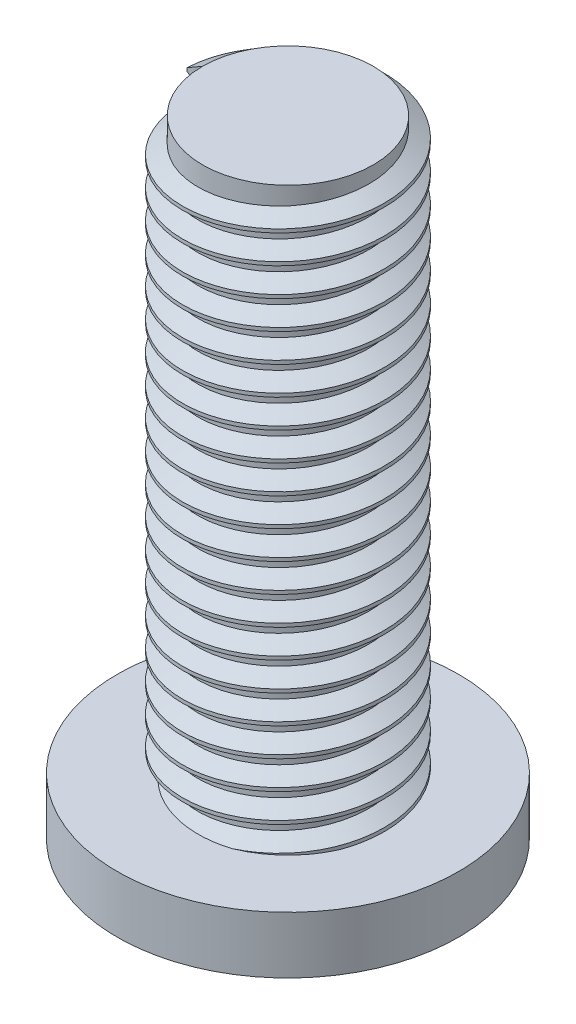
SolidWorks part; units mm, degrees
material "AISI Type A2 Tool Steel"
ref_plane "Front Plane" through (0, 0, 0) normal (0, 0, 1) x (1, 0, 0)
ref_plane "Top Plane" through (0, 0, 0) normal (0, 1, 0) x (1, 0, 0)
ref_plane "Right Plane" through (0, 0, 0) normal (1, 0, 0) x (0, 0, -1)
sketch "Sketch1" plane through (0, 0, 0) normal (0, 1, 0) x (1, 0, 0)
  circle A0 centre (0, 0) radius 1.5
  dimension "D1" = 3
extrude "Boss-Extrude1" add sketch "Sketch1" along normal blind 10
sketch "Sketch2" plane through (0, 0, 0) normal (0, -1, 0) x (1, 0, 0)
  circle A0 centre (0, 0) radius 3
  dimension "D1" = 6
extrude "Boss-Extrude2" add sketch "Sketch2" along normal blind 1
thread "Thread1" pitch 0.5 method extrude profile "Thread Profile1" start angle 0, offset 0, length 0, pitch 0.5, diameter 3
ref_plane "Plane1" through (-1.5, 10, 0) normal (0, 0, 1) x (-1, 0, 0)
sketch "Thread Profile1" plane through (-1.5, 10, 0) normal (0, 0, 1) x (-1, 0, 0)
  line L0 (0, 0) -> (0, 0.5) construction
  line L1 (0, 0) -> (0.2706, 0.1562)
  line L2 (0.2706, 0.1562) -> (0.2706, 0.2187)
  line L3 (0.2706, 0.2187) -> (0, 0.375)
  line L4 (0.2706, 0.1875) -> (0, 0.1875) construction
  line L11 (0, 0) -> (0, 0.375)
  point P2 (0, 0)
  dimension "Pitch" = 0.5
  dimension "Profile_Angle" = 60
  dimension "Profile_Land" = 0.0625
  dimension "Profile_Height" = 0.2706
